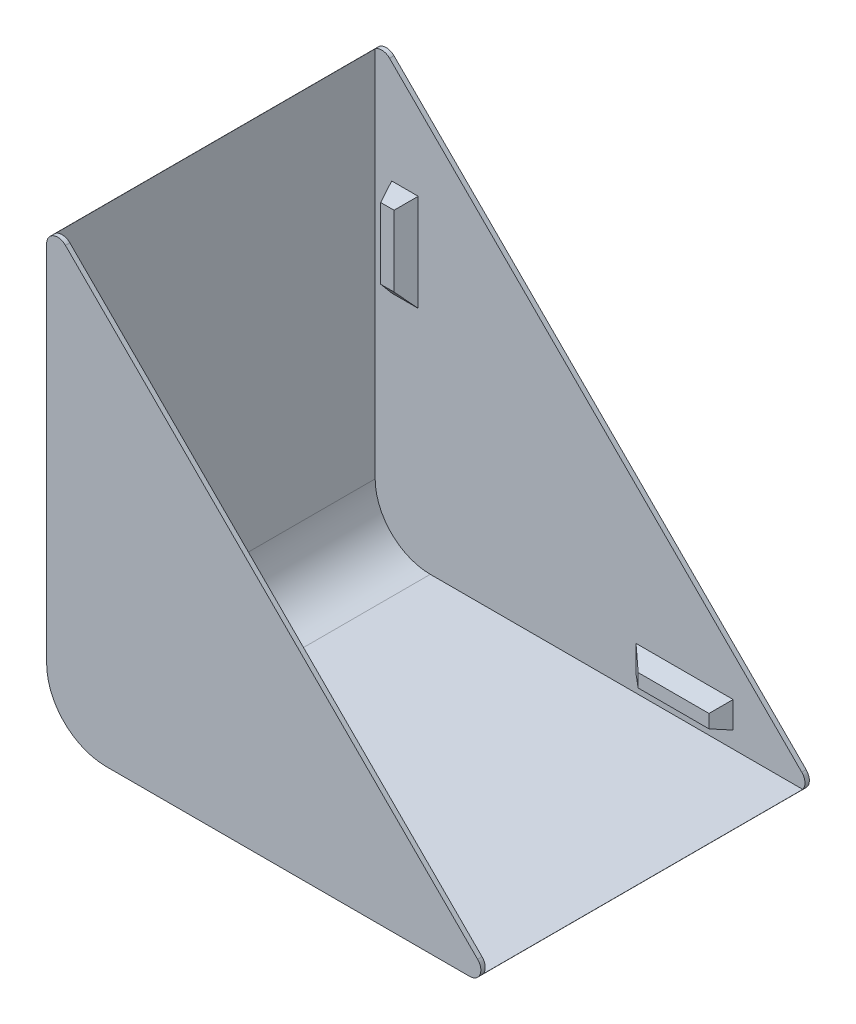
SolidWorks part; units mm, degrees
ref_plane "Plan de face" through (0, 0, 0) normal (0, 0, 1) x (1, 0, 0)
ref_plane "Plan de dessus" through (0, 0, 0) normal (0, 1, 0) x (1, 0, 0)
ref_plane "Plan de droite" through (0, 0, 0) normal (1, 0, 0) x (0, 0, -1)
sketch "Esquisse1" plane through (0, 0, 0) normal (0, 0, 1) x (1, 0, 0)
  line L0 (0, 0) -> (0, 80)
  line L1 (0, 80) -> (80, 0)
  line L2 (80, 0) -> (0, 0)
  dimension "D1" = 80
  dimension "D2" = 80
extrude "Boss.-Extru.1" add sketch "Esquisse1" along normal mid plane 58
sketch "Esquisse4" plane through (0, 0, 0) normal (1, 0, 0) x (0, 0, -1)
  line L0 (-61.9556, 0) -> (61.9556, 0) construction
  point P4 (0, 0)
fillet "Congé1" radius 10 1 edges at (0, 0, 0)
shell "Coque1" thickness 0.8 removed face at (40, 40, 0) outward yes
fillet "Congé2" radius 2 2 edges at (80.8, -0.8, 0) (-0.8, 80.8, 0)
sketch "Esquisse2" plane through (0, 0, 29) normal (0, 0, -1) x (-1, 0, 0)
  line L0 (-66.1349, 3) -> (-66.1349, 9)
  line L1 (-66.1349, 3) -> (-46.1349, 3)
  line L2 (-66.1349, 9) -> (-46.1349, 9)
  line L3 (-46.1349, 3) -> (-46.1349, 9)
  line L4 (-10, 0) -> (-77.5716, 0) construction
  line L5 (-3, 39.4964) -> (-3, 59.4964)
  line L6 (-3, 39.4964) -> (-9, 39.4964)
  line L7 (-3, 59.4964) -> (-9, 59.4964)
  line L8 (-9, 39.4964) -> (-9, 59.4964)
  line L9 (0, 77.5716) -> (0, 10) construction
  arc A0 (-77.3858, 2.6142) -> (-77.5716, 0) centre (-75.9716, 1.2) ccw construction
  dimension "D1" = 3
  dimension "D2" = 20
  dimension "D3" = 6
  dimension "D4" = 10
  dimension "D5" = 20
  dimension "D6" = 3
  dimension "D7" = 6
extrude "Boss.-Extru.2" add sketch "Esquisse2" along normal blind 2
chamfer "Chanfrein1" distance 3 angle 50 6 edges at (56.1349, 9, 27) (66.1349, 6, 27) (46.1349, 6, 27) (6, 39.4964, 27) (6, 59.4964, 27) (9, 49.4964, 27) first distance on face at (56.1349, 9, 28) first distance on face at (66.1349, 6, 28) first distance on face at (46.1349, 6, 28) first distance on face at (6, 39.4964, 28) first distance on face at (6, 59.4964, 28) first distance on face at (9, 49.4964, 28)
mirror "Symétrie1" about plane through (0, 0, 0) normal (0, 0, 1) of "Chanfrein1", "Boss.-Extru.2"
equation "\"longueur\"=80"
equation "\"D1@Esquisse1\"=\"longueur\""
equation "\"D2@Esquisse1\"=\"longueur\""
equation "\"largeur_ext\"=10"
equation "\"D1@Boss.-Extru.1\"=\"largeur_int\""
equation "\"largeur_int\"=58"
equation "\"conges\"=10"
equation "\"D1@Congé1\"=\"conges\""
equation "\"buse\"= 0.4'Buse impression"
equation "\"D1@Coque1\"=\"buse\"*2"
